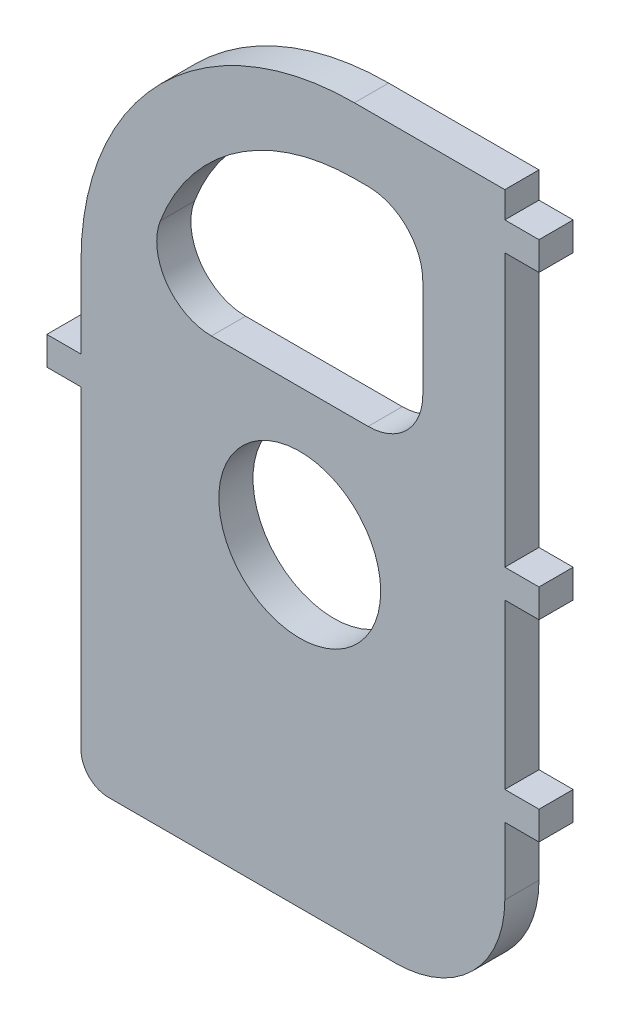
SolidWorks part; units mm, degrees
material "Balsa"
ref_plane "Front Plane" through (0, 0, 0) normal (0, 0, 1) x (1, 0, 0)
ref_plane "Top Plane" through (0, 0, 0) normal (0, 1, 0) x (1, 0, 0)
ref_plane "Right Plane" through (0, 0, 0) normal (1, 0, 0) x (0, 0, -1)
sketch "Sketch1" plane through (0, 0, 0) normal (0, 0, 1) x (1, 0, 0)
  line L0 (0, -1000.1535) -> (0, 48999.8465) construction
  line L2 (-1000, 0) -> (49000, 0) construction
  line L3 (9.525, 16.51) -> (11.1125, 16.51)
  line L4 (2.54, 19.05) -> (9.525, 19.05)
  line L5 (-10.16, 6.35) -> (-10.16, -14.605)
  line L6 (-10.16, -14.605) -> (9.525, -14.605)
  line L7 (9.525, 19.05) -> (9.525, -14.605)
  line L8 (-11.7475, 1.27) -> (-10.16, 1.27)
  line L9 (-11.7475, 1.27) -> (-11.7475, 2.5908)
  line L10 (-11.7475, 2.5908) -> (-10.16, 2.5908)
  line L11 (-10.16, 1.27) -> (-10.16, 2.5908)
  line L12 (9.525, 2.54) -> (11.1125, 2.54)
  line L13 (9.525, 2.54) -> (9.525, 3.8608)
  line L14 (9.525, 3.8608) -> (11.1125, 3.8608)
  line L15 (11.1125, 2.54) -> (11.1125, 3.8608)
  line L16 (9.525, 16.51) -> (9.525, 17.8308)
  line L17 (9.525, 17.8308) -> (11.1125, 17.8308)
  line L18 (11.1125, 16.51) -> (11.1125, 17.8308)
  line L19 (9.525, -5.08) -> (11.1125, -5.08)
  line L20 (9.525, -5.08) -> (9.525, -6.4008)
  line L21 (9.525, -6.4008) -> (11.1125, -6.4008)
  line L22 (11.1125, -5.08) -> (11.1125, -6.4008)
  circle A0 centre (0, 0) radius 3.7592
  arc A3 (2.54, 19.05) -> (-10.16, 6.35) centre (2.54, 6.35) ccw
  dimension "D1" = 7.5184
  dimension "D4" = 14.605
  dimension "D3" = 16.51
  dimension "D5" = 1.5875
  dimension "D9" = 12.7
  dimension "D10" = 1.5875
  dimension "D18" = 1.27
  dimension "D2" = 19.05
  dimension "D6" = 9.525
  dimension "D7" = 1.3208
  dimension "D8" = 19.685
  dimension "D11" = 2.54
  dimension "D12" = 1.3208
  dimension "D13" = 1.3208
  dimension "D14" = 1.5875
  dimension "D19" = 1.5875
  dimension "D20" = 1.3208
  dimension "D21" = 5.08
extrude "Boss-Extrude1" add sketch "Sketch1" along normal blind 1.5875 contours L4 A3 L5 L6 L7 A0 | L10 L9 L8 L5 | L3 L18 L17 L7 | L12 L15 L14 L7 | A3 L5 | L22 L19 L7 L21 region at (10.3187, 17.1704, 0) region at (9.1351, 10.1854, 0) region at (10.3187, 3.2004, 0) region at (10.3187, -5.7404, 0) region at (-10.9538, 1.9304, 0)
fillet "Fillet1" radius 5.08 1 edges at (9.525, -14.605, 0.7937)
fillet "Fillet2" radius 1.27 1 edges at (-10.16, -14.605, 0.7937)
sketch "Sketch2" plane through (0, 0, 1.5875) normal (0, 0, 1) x (1, 0, 0)
  line L0 (-7.112, 6.35) -> (5.715, 6.35)
  line L1 (5.715, 16.002) -> (2.54, 16.002)
  line L2 (5.715, 16.002) -> (5.715, 6.35)
  line L3 (9.525, 16.51) -> (9.525, 3.8608) construction
  arc A2 (2.54, 16.002) -> (-7.112, 6.35) centre (2.54, 6.35) ccw
  arc A3 (2.54, 16.002) -> (-7.112, 6.35) centre (2.54, 6.35) ccw
  dimension "D2" = 3.81
  dimension "D1" = 3.048
extrude "Weight Reduction" cut sketch "Sketch2" against normal up to next
fillet "Fillet3" radius 2.54 3 edges at (5.715, 6.35, 0.7937) (-7.112, 6.35, 0.7937) (5.715, 16.002, 0.7937)
